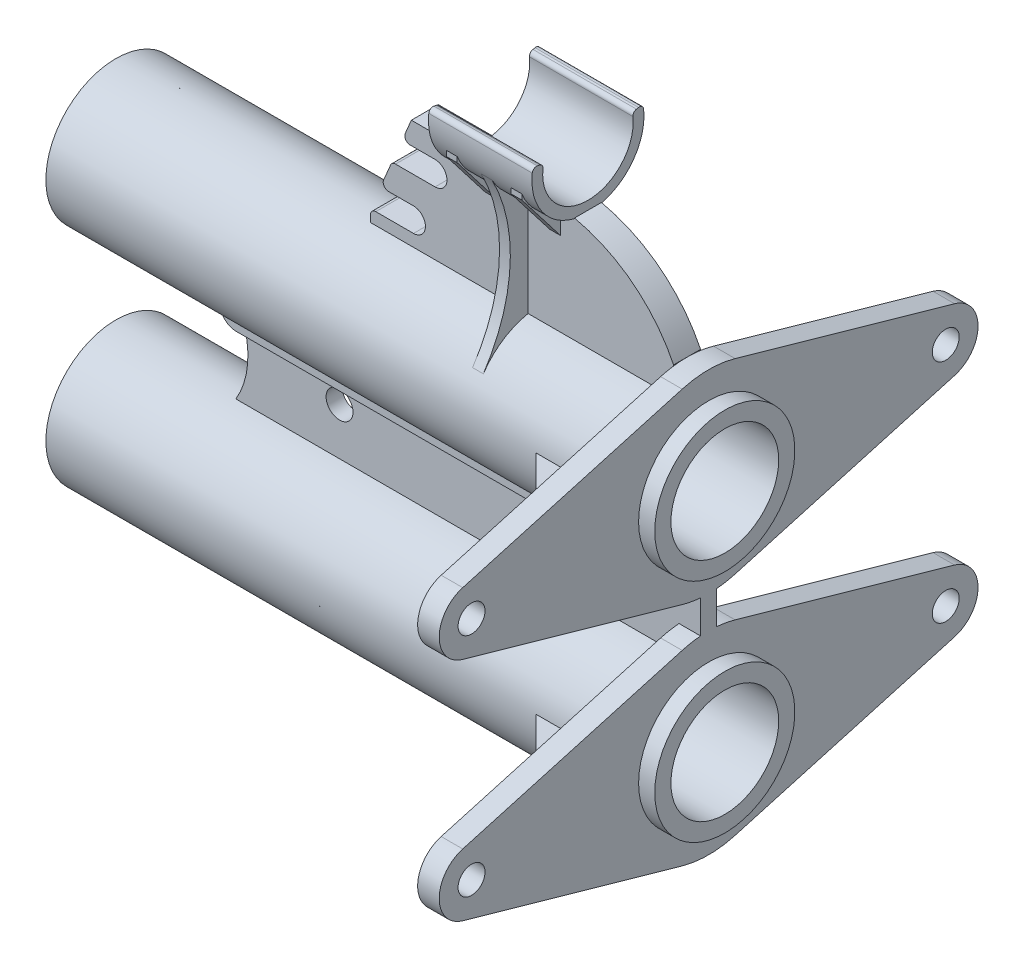
SolidWorks part; units mm, degrees
ref_plane "Front" through (0, 0, 0) normal (0, 0, 1) x (1, 0, 0)
ref_plane "Top" through (0, 0, 0) normal (0, 1, 0) x (1, 0, 0)
ref_plane "Right" through (0, 0, 0) normal (1, 0, 0) x (0, 0, -1)
sketch "Sketch1" plane through (0, 0, 0) normal (1, 0, 0) x (0, 0, -1)
  circle A0 centre (0, 0) radius 8.255
  dimension "D1" = 16.51
extrude "tube" add sketch "Sketch1" against normal blind 69.85
sketch "Sketch2" plane through (0, 0, 0) normal (1, 0, 0) x (0, 0, -1)
  line L0 (27.94, 0) -> (-27.94, 0) construction
  line L1 (-28.9791, 3.6656) -> (-3.1173, 10.9967)
  line L2 (3.1173, 10.9967) -> (28.9791, 3.6656)
  line L3 (28.9791, -3.6656) -> (3.1173, -10.9967)
  line L4 (-28.9791, -3.6656) -> (-3.1173, -10.9967)
  arc A0 (-28.9791, 3.6656) -> (-28.9791, -3.6656) centre (-27.94, 0) ccw
  circle A1 centre (0, 0) radius 11.43
  arc A2 (-3.1173, -10.9967) -> (3.1173, -10.9967) centre (0, 0) ccw
  arc A3 (28.9791, -3.6656) -> (28.9791, 3.6656) centre (27.94, 0) ccw
  arc A4 (3.1173, 10.9967) -> (-3.1173, 10.9967) centre (0, 0) ccw
  circle A5 centre (-27.94, 0) radius 1.5875
  circle A6 centre (27.94, 0) radius 1.5875
  dimension "D2" = 7.62
  dimension "D4" = 3.175
  dimension "D3" = 63.5
  dimension "D1" = 3.175
extrude "flange" add sketch "Sketch2" against normal blind 2.54
sketch "Sketch3" plane through (-69.85, 0, 0) normal (-1, 0, 0) x (0, 0, 1)
  circle A1 centre (0, 0) radius 6.35
  circle A2 centre (0, 0) radius 6.35
  dimension "D1" = 1.905
extrude "hole" cut sketch "Sketch3" against normal through all
sketch "Sketch4" plane through (0, 0, 0) normal (1, 0, 0) x (0, 0, -1)
  circle A0 centre (0, 0) radius 6.35 construction
  circle A1 centre (0, 0) radius 8.255
  circle A2 centre (0, 0) radius 8.255
  circle A3 centre (0, 0) radius 6.35
  dimension "D1" = 1.905
extrude "circular boss" add sketch "Sketch4" along normal blind 1.905
sketch "Sketch6" plane through (0, 0, 0) normal (0, 1, 0) x (1, 0, 0)
  line L0 (-2.54, 7.3025) -> (-13.0175, 7.3025)
  line L1 (-2.54, 7.3025) -> (-2.54, 17.78)
  line L2 (-2.54, 8.255) -> (-69.85, 8.255) construction
  line L4 (-2.54, 3.1173) -> (-2.54, 28.9791) construction
  line L5 (-13.0175, 7.3025) -> (-2.54, 17.78)
  point P7 (-12.065, 8.255)
  dimension "D1" = 0.9525
  dimension "D2" = 9.525
  dimension "D3" = 9.525
extrude "brace" add sketch "Sketch6" along normal mid plane 1.905
mirror "Mirror1" about plane through (0, 0, 0) normal (0, 0, 1) of "brace"
sketch "Sketch5" plane through (0, 0, 0) normal (0, 0, 1) x (1, 0, 0)
  line L0 (0, 7.3025) -> (-55.372, 7.3025)
  line L1 (0, 7.3025) -> (0, 19.3675)
  line L2 (-55.372, 19.3675) -> (0, 19.3675)
  line L3 (-2.54, 8.255) -> (-69.85, 8.255) construction
  line L4 (0, 3.6656) -> (0, 10.9967) construction
  line L5 (-2.54, 8.255) -> (-69.85, 8.255) construction
  line L6 (-63.3105, 18.415) -> (7.5357, 18.415) construction
  arc A0 (-55.372, 7.3025) -> (-55.372, 19.3675) centre (-63.3105, 13.335) ccw
  circle A1 centre (-42.545, 13.7414) radius 1.5875
  circle A2 centre (-12.7, 13.7414) radius 1.5875
  dimension "D6" = 3.175
  dimension "D1" = 0.9525
  dimension "D2" = 53.34
  dimension "D3" = 55.372
  dimension "D4" = 0.9525
  dimension "D5" = 10.16
  dimension "D7" = 12.7
  dimension "D8" = 29.845
  dimension "D9" = 5.4864
extrude "center plate" add sketch "Sketch5" along normal mid plane 1.905
pattern_linear "upper tube&flange" count 2 spacing 26.67 along (0, 1, 0) of "Mirror1", "brace", "tube", "flange", "hole", "circular boss"
sketch "Sketch7" plane through (0, 0, 0) normal (0, 0, 1) x (1, 0, 0)
  line L0 (-33.4455, 47.625) -> (-17.78, 47.625)
  line L1 (-2.54, 34.925) -> (-69.85, 34.925) construction
  line L2 (-2.54, 30.3356) -> (-2.54, 37.6667) construction
  line L3 (-2.54, 33.9725) -> (-2.54, 38.1)
  line L4 (-38.2715, 33.9725) -> (-38.2715, 36.195)
  line L5 (0, 38.1) -> (-2.54, 38.1) construction
  line L6 (-2.54, 33.9725) -> (-69.85, 33.9725)
  line L7 (-2.54, 33.9725) -> (-38.2715, 33.9725)
  line L9 (-38.2715, 36.195) -> (-33.1915, 36.195)
  line L11 (-33.1915, 39.0029) -> (-37.086, 39.0029)
  line L12 (-35.7315, 42.2108) -> (-30.6515, 42.2108)
  line L14 (-30.6515, 45.0187) -> (-34.546, 45.0187)
  line L15 (-34.546, 45.0187) -> (-33.4455, 47.625)
  line L16 (-35.7315, 42.2108) -> (-37.086, 39.0029)
  arc A0 (-2.54, 38.1) -> (-17.78, 47.625) centre (-17.78, 30.6705) ccw
  arc A1 (-33.1915, 39.0029) -> (-33.1915, 36.195) centre (-33.1915, 37.5989) cw
  arc A2 (-30.6515, 42.2108) -> (-30.6515, 45.0187) centre (-30.6515, 43.6147) ccw
  dimension "D3" = 5.08
  dimension "D1" = 12.7
  dimension "D2" = 15.24
  dimension "D5" = 7.62
  dimension "D6" = 1.27
  dimension "D7" = 30.9055
  dimension "D8" = 35.7315
  dimension "D9" = 2.6063
  dimension "D4" = 0.9525
extrude "sight" add sketch "Sketch7" along normal mid plane 3.175
fillet "R025" radius 0.635 4 edges at (-37.086, 39.0029, 0) (-35.7315, 42.2108, 0) (-34.546, 45.0187, 0) (-38.2715, 36.195, 0)
ref_plane "centersupport" through (-20.32, 0, 0) normal (1, 0, 0) x (0, 0, -1)
sketch "Sketch8" plane through (-20.32, 0, 0) normal (1, 0, 0) x (0, 0, -1)
  line L0 (-10.4652, 54.864) -> (5.9346, 54.864) construction
  line L1 (-1.5875, 47.625) -> (1.5875, 47.625) construction
  arc A0 (-6.4807, 54.864) -> (6.4807, 54.864) centre (0, 53.594) ccw
  dimension "D1" = 13.208
  dimension "D2" = 1.27
  dimension "D3" = 0.635
extrude "ammo holder" add sketch "Sketch8" along normal mid plane 12.192 thin thin type one direction reverse wall 1.27
fillet "R020" radius 0.508 4 edges at (-20.32, 54.864, 6.4807) (-20.32, 54.6198, 5.2344) (-20.32, 54.6198, -5.2344) (-20.32, 54.864, -6.4807)
sketch "Sketch9" plane through (-20.32, 0, 0) normal (1, 0, 0) x (0, 0, -1)
  line L0 (1.5875, 38.1) -> (1.5875, 47.2479) construction
  line L1 (0, 50) -> (0, -50) construction
  line L3 (1.5875, 34.7709) -> (1.5875, 47.1836)
  arc A0 (6.8644, 31.2553) -> (1.5875, 34.7709) centre (0, 26.67) ccw
  arc A1 (5.8472, 50.5244) -> (6.8644, 31.2553) centre (22.5693, 41.7457) ccw
  arc A2 (1.5875, 47.1836) -> (6.564, 54.3195) centre (0, 53.594) ccw construction
  circle A3 centre (0, 26.67) radius 8.255 construction
  arc A4 (1.5875, 47.1836) -> (5.8472, 50.5244) centre (0, 53.594) ccw
  dimension "D1" = 3.683
extrude "support" add sketch "Sketch9" against normal mid plane 1.27
ref_plane "brace plane" through (-23.495, 0, 0) normal (-1, 0, 0) x (0, 0, 1)
sketch "Sketch10" plane through (-23.495, 0, 0) normal (-1, 0, 0) x (0, 0, 1)
  line L0 (-1.5875, 44.6436) -> (-6.1428, 50.5345)
  line L2 (-6.1428, 50.5345) -> (-6.1428, 51.1695)
  line L3 (-1.5875, 34.7709) -> (-1.5875, 47.1836) construction
  line L4 (-1.5875, 44.6436) -> (-1.5875, 47.1836)
  line L5 (-1.5875, 47.2479) -> (-1.5875, 38.1) construction
  arc A0 (-6.1428, 51.1695) -> (-1.5875, 47.1836) centre (0, 53.594) ccw
  arc A1 (-6.564, 54.3195) -> (-1.5875, 47.1836) centre (0, 53.594) ccw construction
  arc A2 (-6.6903, 54.3335) -> (-1.618, 47.0604) centre (0, 53.594) ccw
  arc A3 (-6.6903, 54.3335) -> (-0.1539, 46.8648) centre (0, 53.594) ccw construction
  dimension "D1" = 2.54
  dimension "D3" = 0.635
  dimension "D2" = 0.127
extrude "support brace" add sketch "Sketch10" along normal blind 1.27
mirror "Mirror2" about plane through (-20.32, 0, 0) normal (1, 0, 0) of "support brace"
sketch "Sketch11" plane through (-2.54, 0, 0) normal (-1, 0, 0) x (0, 0, 1)
  line L0 (-0.9525, 15.2798) -> (-0.9525, 18.4701) construction
  line L1 (-0.9525, 17.0203) -> (-0.9525, 18.4701)
  line L4 (-2.8575, 17.0203) -> (-0.9525, 17.0203)
  line L5 (-2.8575, 17.0203) -> (-2.8575, 18.9253)
  arc A0 (-8.1999, 25.7175) -> (-0.9525, 18.4701) centre (0, 26.67) ccw construction
  arc A1 (-2.8575, 18.9253) -> (-0.9525, 18.4701) centre (0, 26.67) ccw
  dimension "D1" = 1.905
  dimension "D2" = 1.905
extrude "rail" add sketch "Sketch11" along normal up to surface (51.5061 mm away) up to face at (-54.052, 13.335, -0.4762)
fillet "R075" radius 1.905 1 edges at (-54.0461, 17.0203, -1.905)
mirror "Mirror3" about plane through (0, 0, 0) normal (0, 0, 1) of "R075", "rail", "support", "support brace", "Mirror2"
sketch "Sketch12" [suppressed] plane through (0, 0, 0) normal (0, 1, 0) x (1, 0, 0)
  line L0 (-69.85, 8.255) -> (-69.85, -8.255) construction
  line L1 (-69.85, 0) -> (1.905, 0)
  line L2 (-69.85, 0) -> (-69.85, -31.75)
  line L3 (-69.85, -31.75) -> (1.905, -31.75)
  line L4 (1.905, 0) -> (1.905, -31.75)
  line L5 (1.905, -8.255) -> (1.905, 8.255) construction
  line L6 (-2.54, -31.75) -> (0, -31.75) construction
extrude "Cut-Extrude1" [suppressed] cut sketch "Sketch12" against normal through all and the other way through all
